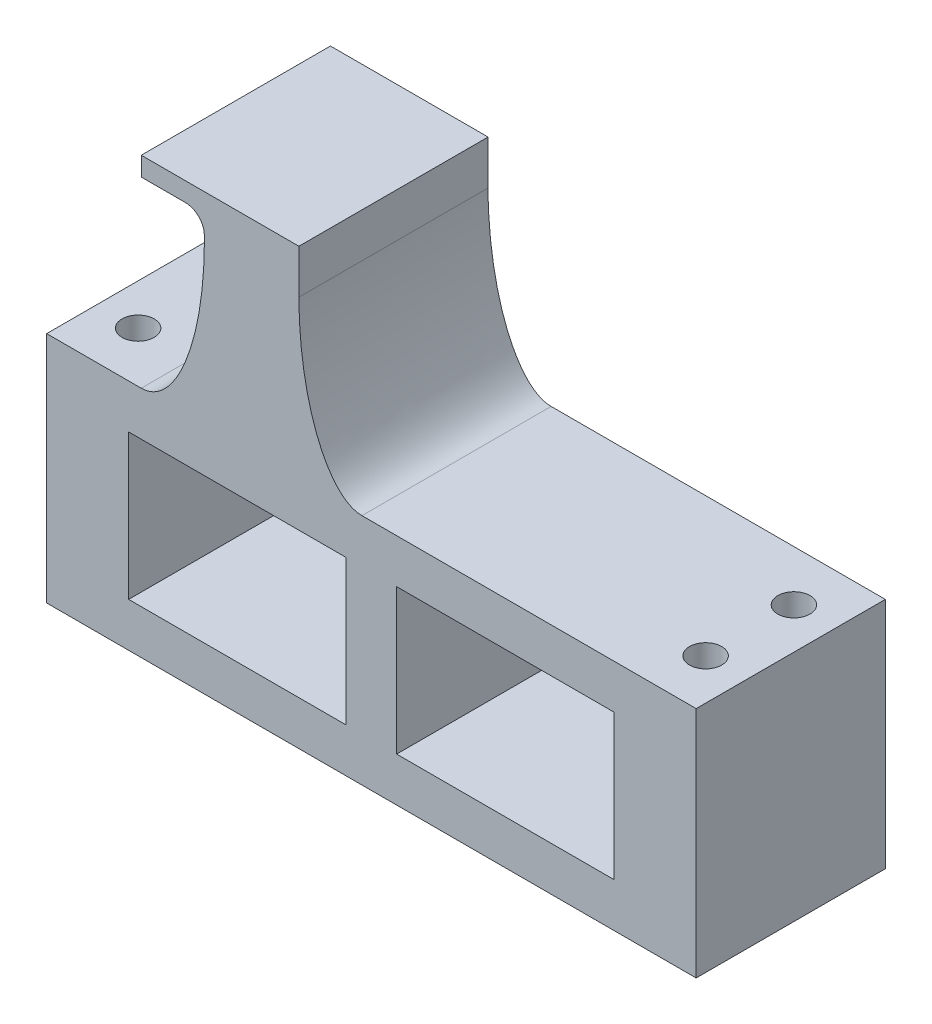
SolidWorks part; units mm, degrees
ref_plane "Front Plane" through (0, 0, 0) normal (0, 0, 1) x (1, 0, 0)
ref_plane "Top Plane" through (0, 0, 0) normal (0, 1, 0) x (1, 0, 0)
ref_plane "Right Plane" through (0, 0, 0) normal (1, 0, 0) x (0, 0, -1)
sketch "Sketch1" plane through (0, 0, 0) normal (0, 1, 0) x (1, 0, 0)
  line L1 (0, 0) -> (103, 0)
  line L2 (0, 0) -> (0, 30)
  line L3 (0, 30) -> (103, 30)
  line L4 (103, 0) -> (103, 30)
  dimension "D1" = 103
  dimension "D2" = 30
extrude "Boss-Extrude1" add sketch "Sketch1" along normal blind 7 contours L1 L4 L3 L2
sketch "Sketch2" plane through (0, 7, 0) normal (0, 1, 0) x (1, 0, 0)
  line L0 (0, 30) -> (103, 30) construction
  line L1 (0, 0) -> (13, 0)
  line L2 (0, 0) -> (0, 30)
  line L3 (0, 30) -> (13, 30)
  line L4 (13, 0) -> (13, 30)
  line L5 (51.5, 0) -> (51.5, 30) construction
  line L6 (0, 0) -> (103, 0) construction
  line L7 (55.5, 30) -> (55.5, 0)
  line L8 (55.5, 30) -> (47.5, 30)
  line L9 (51.5, 30) -> (51.5, 0)
  line L10 (55.5, 0) -> (47.5, 0)
  line L11 (47.5, 30) -> (47.5, 0)
  line L12 (103, 30) -> (90, 30)
  line L13 (103, 0) -> (90, 0)
  line L14 (103, 0) -> (103, 30)
  line L15 (90, 0) -> (90, 30)
  line M9 (0, 30) -> (0, 0)
  line M10 (0, 0) -> (103, 0)
  line M11 (103, 0) -> (103, 30)
  line M12 (103, 30) -> (0, 30)
  dimension "D1" = 13
  dimension "D2" = 4
extrude "Boss-Extrude2" add sketch "Sketch2" along normal blind 23 contours L4 M10 M12 M9 | L8 L11 L9 M10 | L9 L7 M12 M10 | L15 M10 M11 M12 region at (6.5, 7, -15) region at (49.5, 7, -15) region at (53.5, 7, -15) region at (96.5, 7, -15)
sketch "Sketch3" plane through (0, 30, 0) normal (0, 1, 0) x (1, 0, 0)
  line L1 (0, 0) -> (103, 0)
  line L2 (0, 0) -> (0, 30)
  line L3 (0, 30) -> (103, 30)
  line L4 (103, 0) -> (103, 30)
extrude "Boss-Extrude3" add sketch "Sketch3" along normal blind 7
sketch "Sketch4" plane through (0, 37, 0) normal (0, 1, 0) x (1, 0, 0)
  line L0 (0, 30) -> (0, 0) construction
  line L1 (25, 0) -> (40, 0)
  line L2 (25, 0) -> (25, 30)
  line L3 (25, 30) -> (40, 30)
  line L4 (40, 0) -> (40, 30)
  line L5 (0, 0) -> (103, 0) construction
  line L6 (103, 30) -> (0, 30) construction
  dimension "D1" = 25
  dimension "D2" = 15
extrude "Boss-Extrude4" add sketch "Sketch4" along normal blind 29
sketch "Sketch5" plane through (0, 66, 0) normal (0, 1, 0) x (1, 0, 0)
  line L0 (40, 0) -> (40, 30) construction
  line L1 (15, 30) -> (40, 30)
  line L2 (15, 30) -> (15, 0)
  line L3 (15, 0) -> (40, 0)
  line L4 (40, 30) -> (40, 0)
  line L5 (25, 0) -> (40, 0) construction
  line L6 (40, 30) -> (25, 30) construction
  dimension "D2" = 25
extrude "Boss-Extrude5" add sketch "Sketch5" along normal blind 3
fillet "Fillet2" radius 3 1 edges at (25, 66, -15)
fillet "Fillet3" radius 10 2 edges at (40, 37, -15) (25, 37, -15) second distance 25 first distance on face at (71.5, 37, -15) first distance on face at (12.5, 37, -15)
sketch "Sketch6" plane through (0, 0, 0) normal (0, -1, 0) x (1, 0, 0)
  line L0 (0, 0) -> (0, -30) construction
  line L1 (0, -30) -> (103, -30) construction
  line L2 (0, -15) -> (103, -15) construction
  line L3 (103, 0) -> (103, -30) construction
  line L4 (51.5, -30) -> (51.5, 0) construction
  line L5 (0, 0) -> (103, 0) construction
  circle A0 centre (6.5, -22) radius 2.55
  circle A1 centre (6.5, -8) radius 2.55
  circle A2 centre (96.5, -8) radius 2.55
  circle A3 centre (96.5, -22) radius 2.55
  dimension "D1" = 5.1
  dimension "D2" = 6.5
  dimension "D3" = 8
extrude "Cut-Extrude1" cut sketch "Sketch6" against normal blind 40
